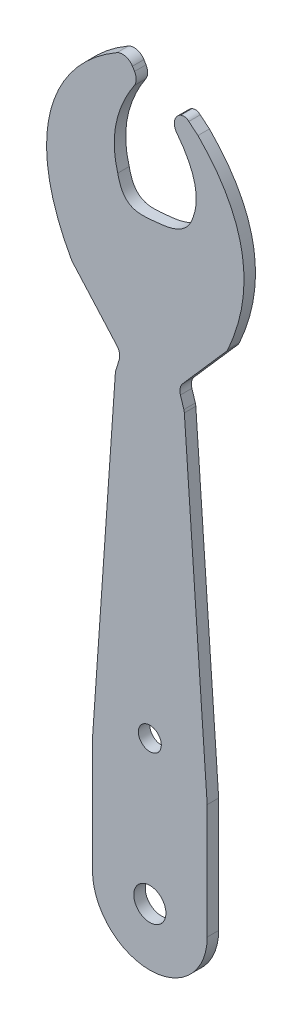
SolidWorks part; units mm, degrees
ref_plane "Alzado" through (0, 0, 0) normal (0, 0, 1) x (1, 0, 0)
ref_plane "Planta" through (0, 0, 0) normal (0, 1, 0) x (1, 0, 0)
ref_plane "Vista lateral" through (0, 0, 0) normal (1, 0, 0) x (0, 0, -1)
sketch "Model" plane through (0, 0, 0) normal (0, 0, 1) x (1, 0, 0)
  line L0 (43.8714, 46.4289) -> (43.6883, 46.7314)
  line L1 (38.4834, 29.3112) -> (42.3324, 24.9607)
  line L2 (42.538, 24.0001) -> (42.2409, 23.0482)
  line L3 (42.1979, 22.8197) -> (40.206, -5.7616)
  line L4 (40.206, -5.7616) -> (40.206, -15.7616)
  line L5 (50.206, -15.7616) -> (50.206, -5.7616)
  line L6 (50.206, -5.7616) -> (48.2141, 22.8197)
  line L7 (48.1711, 23.0482) -> (47.8731, 24.0031)
  line L8 (48.0756, 24.9601) -> (51.8603, 29.2791)
  line L9 (49.3997, 44.3539) -> (48.603, 45.0154)
  circle A0 centre (45.206, -15.7616) radius 1.4
  circle A1 centre (45.206, -3.2616) radius 1
  arc A2 (43.6883, 46.7314) -> (42.3332, 47.0795) centre (42.8329, 46.2133) ccw
  arc A3 (38.3597, 29.4854) -> (38.4834, 29.3112) centre (39.2323, 29.9738) ccw
  arc A4 (42.538, 24.0001) -> (42.3324, 24.9607) centre (41.5834, 24.298) ccw
  arc A5 (42.2409, 23.0482) -> (42.1979, 22.8197) centre (43.1954, 22.7502) ccw
  arc A6 (40.206, -15.7616) -> (50.206, -15.7616) centre (45.206, -15.7616) ccw
  arc A7 (48.2141, 22.8197) -> (48.1711, 23.0482) centre (47.2165, 22.7502) ccw
  arc A8 (48.0756, 24.9601) -> (47.8731, 24.0031) centre (48.8276, 24.301) ccw
  arc A9 (51.8603, 29.2791) -> (52.0208, 29.5293) centre (51.1082, 29.9382) ccw
  arc A10 (47.876, 45.1298) -> (47.5358, 43.6487) centre (48.3395, 44.2437) ccw
  arc A11 (43.8517, 45.3615) -> (43.8714, 46.4289) centre (43.0161, 45.9109) ccw
  spline S0 degree 3 poles (42.3332, 47.0795) (40.7644, 46.1745) (35.8165, 41.9007) (35.2721, 35.0019) (38.3597, 29.4854) knots 0.004003 0.004003 0.004003 0.004003 0.255811 0.955466 0.955466 0.955466 0.955466
  spline S1 degree 3 poles (52.0208, 29.5293) (53.2437, 32.2584) (54.1006, 37.5434) (51.5778, 42.1664) (49.3997, 44.3539) knots 0.073239 0.073239 0.073239 0.073239 0.521566 0.992418 0.992418 0.992418 0.992418
  spline S2 degree 3 poles (48.603, 45.0154) (48.417, 45.2048) (48.1747, 45.2429) (47.876, 45.1298) knots 0 0 0 0 1 1 1 1
  spline S3 degree 3 poles (47.5358, 43.6487) (49.1165, 41.6205) (49.634, 39.7324) (48.9682, 37.939) knots 0 0 0 0 0.676847 0.676847 0.676847 0.676847
  spline S4 degree 3 poles (48.9682, 37.939) (48.4075, 36.2495) (45.5173, 35.9596) (42.8792, 35.7355) (42.4075, 38.0175) knots 0 0 0 0 0.520046 1 1 1 1
  spline S5 degree 3 poles (42.4075, 38.0175) (42.3228, 38.3081) (41.7732, 40.6942) (42.3981, 43.1508) (43.8517, 45.3615) knots 0.047028 0.047028 0.047028 0.047028 0.131515 0.738211 0.738211 0.738211 0.738211
base flange "Brida base1" sketch "Model" thickness 1 reverse thickness direction no parameters "D1"=0.7366
sketch "Líneas de pliegue1" [suppressed] plane through (0, 0, 0) normal (0, 1, 0) x (1, 0, 0)
sketch "Cuadro delimitador1" [suppressed] plane through (0, 0, 0) normal (0, 1, 0) x (1, 0, 0)
sheet metal parameters "Chapa metálica1" thickness 1 parameters "D1"=0.7366
flat pattern "Chapa desplegada1" [suppressed]
sketch "Líneas de pliegue2" plane through (0, 0, 0) normal (0, 1, 0) x (1, 0, 0)
sketch3d "Cuadro delimitador2" [suppressed]
  line L0 (-15.9455, 8.137, 0) -> (-21.1159, -59.6417, 0) construction
  line L1 (1.121, 6.8351, 0) -> (-4.0494, -60.9437, 0) construction
  line L2 (-15.9455, 8.137, 0) -> (1.121, 6.8351, 0) construction
  line L3 (-21.1159, -59.6417, 0) -> (-4.0494, -60.9437, 0) construction
